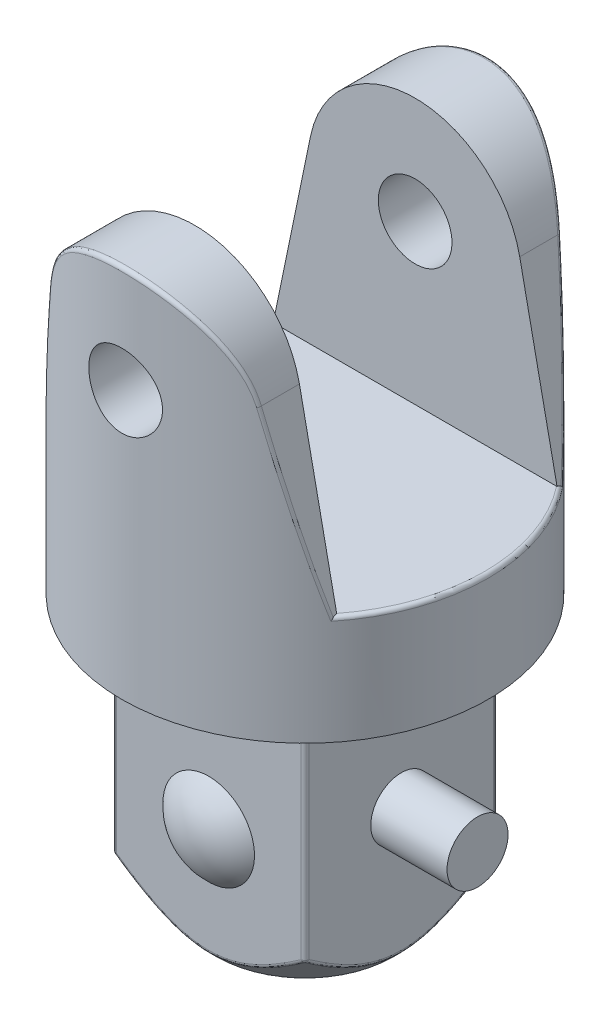
SolidWorks part; units mm, degrees
material "1023 Carbon Steel Sheet (SS)"
ref_plane "Front Plane" through (0, 0, 0) normal (0, 0, 1) x (1, 0, 0)
ref_plane "Top Plane" through (0, 0, 0) normal (0, 1, 0) x (1, 0, 0)
ref_plane "Right Plane" through (0, 0, 0) normal (1, 0, 0) x (0, 0, -1)
sketch "Sketch1" plane through (0, 0, 0) normal (0, 1, 0) x (1, 0, 0)
  circle A0 centre (0, 0) radius 12
  dimension "D1" = 24
extrude "Boss-Extrude1" add sketch "Sketch1" along normal blind 33.53
sketch "Sketch2" plane through (0, 0, 0) normal (0, -1, 0) x (1, 0, 0)
  line L0 (-2.5, 6.5) -> (-6.1, 6.5)
  line L1 (6.5, -6.5) -> (-6.5, -6.5) construction
  line L2 (6.5, -6.5) -> (6.5, 6.5) construction
  line L3 (-6.5, 6.1) -> (-6.5, 2.5)
  line L4 (-6.5, -6.5) -> (-6.5, 6.5) construction
  line L5 (6.5, -6.5) -> (-6.5, 6.5) construction
  line L6 (6.5, 6.5) -> (-6.5, -6.5) construction
  line L7 (-6.5, -2.5) -> (-6.5, -6.1)
  line L8 (-6.1, -6.5) -> (-2.5, -6.5)
  line L9 (2.5, -6.5) -> (6.1, -6.5)
  line L10 (6.5, -6.1) -> (6.5, -2.5)
  line L11 (6.5, 2.5) -> (6.5, 6.1)
  line L12 (6.1, 6.5) -> (2.5, 6.5)
  line L13 (-6.1, 6.5) -> (-6.5, 6.1)
  line L14 (-6.5, -6.1) -> (-6.1, -6.5)
  line L15 (6.1, -6.5) -> (6.5, -6.1)
  line L16 (6.5, 6.1) -> (6.1, 6.5)
  arc A0 (-2.5, 6.5) -> (2.5, 6.5) centre (0, 2.5201) cw
  arc A1 (6.5, 2.5) -> (6.5, -2.5) centre (2.5201, 0) cw
  arc A2 (2.5, -6.5) -> (-2.5, -6.5) centre (0, -2.5201) cw
  arc A3 (-6.5, -2.5) -> (-6.5, 2.5) centre (-2.5201, 0) cw
  point P0 (0, 0)
  point P21 (0, 0)
  dimension "D3" = 4.7
  dimension "D4" = 4
  dimension "D1" = 13
  dimension "D2" = 4
extrude "Cut-Extrude1" cut sketch "Sketch2" against normal blind 19.6
sketch "Sketch3" plane through (0, 0, 0) normal (0, -1, 0) x (1, 0, 0)
  circle A0 centre (0, 0) radius 9.375
  dimension "D1" = 18.75
extrude "Cut-Extrude2" cut sketch "Sketch3" against normal blind 3.4 draft 35
fillet "Fillet1" radius 1.25 1 edges at (0, 0, 12)
sketch "Sketch4" plane through (0, 0, 0) normal (0, 0, 1) x (1, 0, 0)
  line L0 (-7.2, 5.7) -> (-7.2, 4.7)
  line L1 (-7.2, 4.7) -> (-6.6396, 4.9757)
  line L2 (-6.6396, 5.4243) -> (-7.2, 5.7)
  line L3 (-6.5, 19.6) -> (-6.5, 3.4) construction
  arc A0 (-6.6396, 4.9757) -> (-6.6396, 5.4243) centre (-6.75, 5.2) ccw
  point P5 (-6.1837, 5.2)
  dimension "D3" = 0.25
  dimension "D1" = 1
  dimension "D2" = 7.2
  dimension "D4" = 4.7
extrude "Boss-Extrude2" add sketch "Sketch4" against normal up to surface and the other way up to surface up to face at (-6.751, 8.7478, -0.0702) other way up to face at (-6.751, 8.7478, -0.0702)
ref_axis "Axis1" through (0, 35.2065, 0) along (0, -1, 0)
pattern_circular "CirPattern2" count 4 over 360 about axis through (0, 35.2065, 0) along (0, -1, 0) of "Boss-Extrude2"
sketch "Sketch5" plane through (0, 33.53, 0) normal (0, 1, 0) x (1, 0, 0)
  line L1 (12, -7.2201) -> (-12, -7.2201)
  line L2 (12, -7.2201) -> (12, 7.2201)
  line L3 (12, 7.2201) -> (-12, 7.2201)
  line L4 (-12, -7.2201) -> (-12, 7.2201)
  line L5 (12, -7.2201) -> (-12, 7.2201) construction
  line L6 (12, 7.2201) -> (-12, -7.2201) construction
  arc A0 (2.5, 6.5) -> (-2.5, 6.5) centre (0, 2.5201) ccw construction
  circle A1 centre (0, 0) radius 12 construction
  point P0 (0, 0)
extrude "Cut-Extrude3" cut sketch "Sketch5" against normal blind 17.4
sketch "Sketch6" plane through (0, 0, 0) normal (0, 0, 1) x (1, 0, 0)
  line L0 (12, 16.13) -> (9.3, 16.13)
  line L1 (9.3, 16.13) -> (6.8548, 27.9483)
  line L2 (-6.8548, 27.9483) -> (-9.3, 16.13)
  line L3 (-9.3, 16.13) -> (-12, 16.13)
  line L4 (9.5849, 33.53) -> (-9.5849, 33.53) construction
  arc A0 (6.8548, 27.9483) -> (-6.8548, 27.9483) centre (0, 26.53) ccw
  dimension "D2" = 7
  dimension "D1" = 2.7
extrude "Cut-Extrude6" cut sketch "Sketch6" against normal through all both and the other way through all flip side to cut
sketch "Sketch7" plane through (0, 0, 0) normal (0, 0, 1) x (1, 0, 0)
  circle A0 centre (0, 26.53) radius 2.415
  dimension "D1" = 4.83
extrude "Cut-Extrude7" cut sketch "Sketch7" against normal mid plane 52.4
fillet "Fillet2" radius 0.25 8 edges at (-8.1565, 21.657, -8.8018) (8.1565, 21.657, -8.8018) (8.1565, 21.657, 8.8018) (-8.1565, 21.657, 8.8018) (-12, 16.13, 0) (0, 33.53, -12) (12, 16.13, 0) (0.1168, 33.529, 11.9994)
sketch "Sketch8" plane through (0, 0, 0) normal (0, 1, 0) x (1, 0, 0)
  circle A1 centre (0, 0) radius 12 construction
  circle A2 centre (0, 0) radius 12
extrude "Cut-Extrude8" cut sketch "Sketch8" along normal blind 9
sketch "Sketch10" plane through (0, 9, 0) normal (0, -1, 0) x (1, 0, 0)
  line L0 (-6.1, -6.5) -> (-2.5, -6.5) construction
  line L1 (-6.1, -6.5) -> (-2.5, -6.5)
  line L2 (-6.5, -2.5) -> (-6.5, -6.1) construction
  line L3 (2.5, -6.5) -> (6.1, -6.5) construction
  line L4 (6.1, -6.5) -> (6.5, -6.1) construction
  line L5 (6.5, -6.1) -> (6.5, -2.5) construction
  line L6 (6.5, 2.5) -> (6.5, 6.1) construction
  line L7 (6.5, 6.1) -> (6.1, 6.5) construction
  line L8 (6.1, 6.5) -> (2.5, 6.5) construction
  line L9 (-2.5, 6.5) -> (-6.1, 6.5) construction
  line L10 (-6.1, 6.5) -> (-6.5, 6.1) construction
  line L11 (-6.5, 6.1) -> (-6.5, 2.5) construction
  line L12 (-6.5, -6.1) -> (-6.1, -6.5) construction
  line L13 (-6.5, -2.5) -> (-6.5, -6.1)
  line L14 (2.5, -6.5) -> (6.1, -6.5)
  line L15 (6.1, -6.5) -> (6.5, -6.1)
  line L16 (6.5, -6.1) -> (6.5, -2.5)
  line L17 (6.5, 2.5) -> (6.5, 6.1)
  line L18 (6.5, 6.1) -> (6.1, 6.5)
  line L19 (6.1, 6.5) -> (2.5, 6.5)
  line L20 (-2.5, 6.5) -> (-6.1, 6.5)
  line L21 (-6.1, 6.5) -> (-6.5, 6.1)
  line L22 (-6.5, 6.1) -> (-6.5, 2.5)
  line L23 (-6.5, -6.1) -> (-6.1, -6.5)
  arc A0 (-2.5, -6.5) -> (2.5, -6.5) centre (0, -2.5201) ccw construction
  arc A3 (6.5, -2.5) -> (6.5, 2.5) centre (2.5201, 0) ccw construction
  arc A4 (2.5, 6.5) -> (-2.5, 6.5) centre (0, 2.5201) ccw construction
  arc A5 (-6.5, 2.5) -> (-6.5, -2.5) centre (-2.5201, 0) ccw construction
  arc A6 (-2.5, -6.5) -> (2.5, -6.5) centre (0, -2.5201) ccw
  arc A7 (6.5, -2.5) -> (6.5, 2.5) centre (2.5201, 0) ccw
  arc A8 (2.5, 6.5) -> (-2.5, 6.5) centre (0, 2.5201) ccw
  arc A9 (-6.5, 2.5) -> (-6.5, -2.5) centre (-2.5201, 0) ccw
extrude "Boss-Extrude4" add sketch "Sketch10" against normal up to surface (7.13 mm away) up to face at (-5.4201, 16.13, 0)
sketch "Sketch11" plane through (0, 9, 0) normal (0, -1, 0) x (1, 0, 0)
  line L1 (6.31, -6.31) -> (-6.31, -6.31)
  line L2 (6.31, -6.31) -> (6.31, 6.31)
  line L3 (6.31, 6.31) -> (-6.31, 6.31)
  line L4 (-6.31, -6.31) -> (-6.31, 6.31)
  line L5 (6.31, -6.31) -> (-6.31, 6.31) construction
  line L6 (6.31, 6.31) -> (-6.31, -6.31) construction
  point P0 (0, 0)
  dimension "D1" = 12.62
extrude "Boss-Extrude5" add sketch "Sketch11" along normal blind 17.8
sketch "Sketch12" plane through (0, 0, 0) normal (0, 0, 1) x (1, 0, 0)
  line L0 (-5.7, -8.8) -> (-12.0795, -2.4205)
  line L1 (6.31, -8.8) -> (-6.31, -8.8) construction
  line L2 (-12.0795, -2.4205) -> (-12.0795, -8.8)
  line L3 (-12.0795, -8.8) -> (-5.7, -8.8)
  dimension "D1" = 5.7
  dimension "D2" = 45
revolve "Cut-Revolve1" cut sketch "Sketch12" angle 360 about axis through (0, 35.2065, 0) along (0, -1, 0)
chamfer "Chamfer1" distance 1.25 angle 45 4 edges at (0, 9, -6.31) (6.31, 9, 0) (-6.31, 9, 0) (0, 9, 6.31)
fillet "Fillet3" radius 0.25 9 edges at (-6.31, 1.0868, 6.31) (0.7237, -8.1486, 6.31) (6.31, -8.1486, 0.7237) (6.31, 1.0868, -6.31) (0, -8.8, 5.7) (6.31, 1.0868, 6.31) (-6.31, -8.1486, 0.7237) (0.7237, -8.1486, -6.31) (-6.31, 1.0868, -6.31)
sketch "Sketch14" plane through (0, 0, 0) normal (1, 0, 0) x (0, 0, -1)
  line L0 (-6.31, -1.2) -> (-6.31, -4.2)
  line L1 (-6.31, 7.75) -> (-6.31, -5.5763) construction
  line L2 (-6.31, -1.2) -> (-7.66, -1.2)
  line L4 (-5.5964, -8.8) -> (5.5964, -8.8) construction
  arc A0 (-7.66, -1.2) -> (-6.31, -4.2) centre (-3.6517, -1.2) ccw
  dimension "D1" = 3
  dimension "D2" = 1.35
  dimension "D3" = 7.6
revolve "Revolve1" add sketch "Sketch14" angle 360 about L2
sketch "Sketch15" plane through (6.31, 0, 0) normal (1, 0, 0) x (0, 0, -1)
  circle A0 centre (0, 0) radius 2
sketch "Sketch16" plane through (-6.31, 0, 0) normal (-1, 0, 0) x (0, 0, 1)
  circle A0 centre (0, 0) radius 2
extrude "Boss-Extrude6" add sketch "Sketch16" along normal blind 5
extrude "Boss-Extrude7" add sketch "Sketch15" along normal blind 5 contours A0
